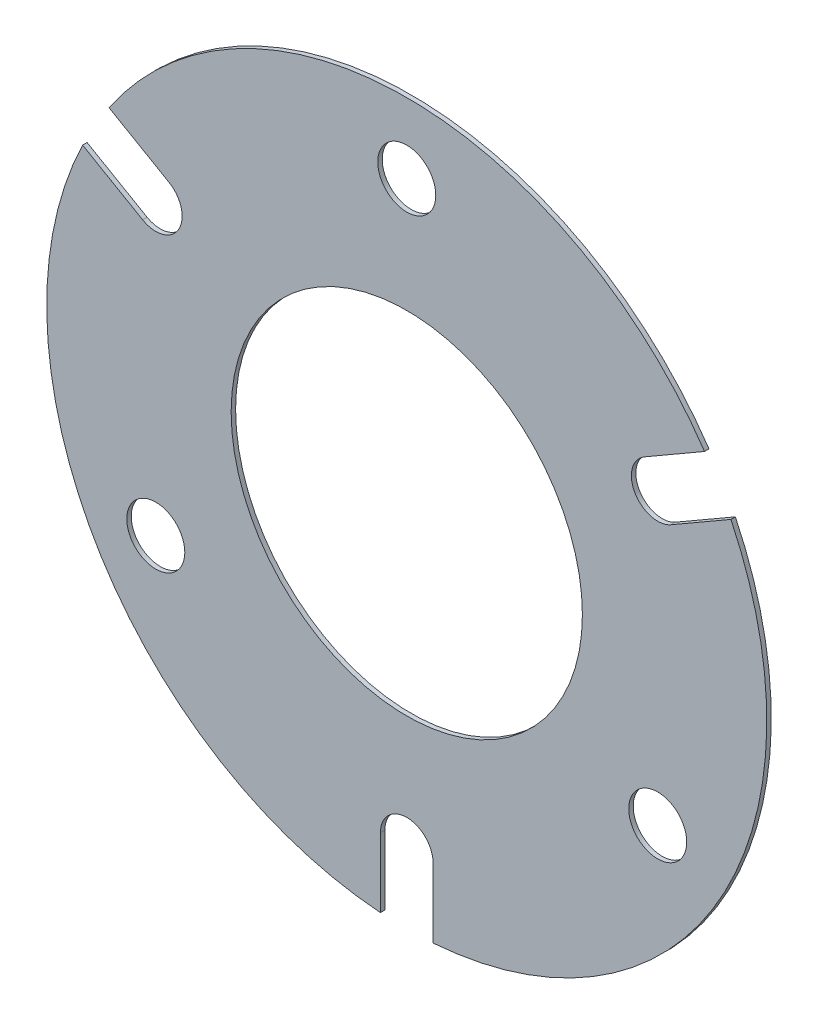
SolidWorks part; units mm, degrees
material "AISI 316 Annealed Stainless Steel Bar (SS)"
ref_plane "Front Plane" through (0, 0, 0) normal (0, 0, 1) x (1, 0, 0)
ref_plane "Top Plane" through (0, 0, 0) normal (0, 1, 0) x (1, 0, 0)
ref_plane "Right Plane" through (0, 0, 0) normal (1, 0, 0) x (0, 0, -1)
sketch "Sketch1" plane through (0, 0, 0) normal (0, 0, 1) x (1, 0, 0)
  circle A0 centre (0, 0) radius 20.5
  circle A1 centre (0, 0) radius 10
  circle A2 centre (0, 16.5) radius 1.651
  circle A3 centre (14.2894, -8.25) radius 1.651
  circle A4 centre (-14.2894, -8.25) radius 1.651
  circle A5 centre (0, 0) radius 16.5 construction
  dimension "D1" = 20
  dimension "D2" = 16.5
  dimension "D3" = 3.302
  dimension "D4" = 41
  dimension "D5" = 3
extrude "Extrude1" add sketch "Sketch1" along normal blind 0.254
sketch "Sketch4" plane through (0, 0, 0) normal (0, 0, -1) x (-1, 0, 0)
  line L0 (1.5, -16.5) -> (1.5, -20.445)
  line L1 (-1.5, -16.5) -> (-1.5, -20.445)
  circle A0 centre (0, 0) radius 16.5 construction
  circle A1 centre (0, 0) radius 20.5
  circle A2 centre (0, 0) radius 20.5
  circle A3 centre (0, -16.5) radius 1.5
  circle M4 centre (0, 0) radius 20.5
  dimension "D2" = 3
  dimension "D1" = 0
extrude "Cut-Extrude1" cut sketch "Sketch4" against normal through all contours A3 L1 L0 M4 | A3 region at (0, -16.5, 0) region at (0, -19.06, 0)
ref_axis "Axis1" through (0, 0, 0.254) along (0, 0, -1)
pattern_circular "CirPattern1" count 3 over 360 about axis through (0, 0, 0.254) along (0, 0, -1) of "Cut-Extrude1"
